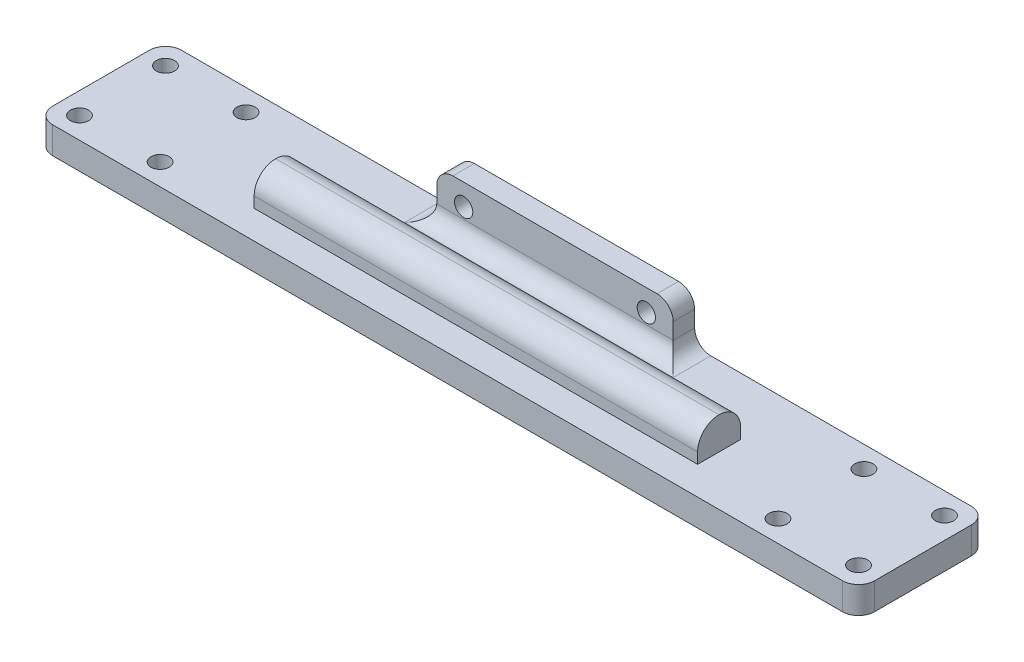
SolidWorks part; units mm, degrees
ref_plane "Front Plane" through (0, 0, 0) normal (0, 0, 1) x (1, 0, 0)
ref_plane "Top Plane" through (0, 0, 0) normal (0, 1, 0) x (1, 0, 0)
ref_plane "Right Plane" through (0, 0, 0) normal (1, 0, 0) x (0, 0, -1)
sketch "Sketch1" plane through (0, 0, 0) normal (0, 1, 0) x (1, 0, 0)
  line L5 (-76.5, -12) -> (-53.5, -12)
  line L13 (-76.5, 12) -> (-53.5, 12)
  line L14 (-76.5, -12) -> (-76.5, 12)
  line L15 (53.5, -12) -> (76.5, -12)
  line L22 (76.5, -12) -> (76.5, 12)
  line L23 (53.5, 12) -> (76.5, 12)
  line L26 (-53.5, 12) -> (53.5, 12)
  line L28 (-53.5, -12) -> (53.5, -12)
  circle A5 centre (-72.5, 8) radius 1.7
  circle A6 centre (-57.5, 8) radius 1.7
  circle A7 centre (-57.5, -8) radius 1.7
  circle A8 centre (-72.5, -8) radius 1.7
  circle A10 centre (57.5, 8) radius 1.7
  circle A11 centre (72.5, 8) radius 1.7
  circle A12 centre (72.5, -8) radius 1.7
  circle A13 centre (57.5, -8) radius 1.7
extrude "Boss-Extrude1" add sketch "Sketch1" along normal blind 5
fillet "Fillet1" radius 3 4 edges at (76.5, 2.5, 12) (76.5, 2.5, -12) (-76.5, 2.5, -12) (-76.5, 2.5, 12)
sketch "Sketch2" plane through (0, 5, 0) normal (0, 1, 0) x (1, 0, 0)
  line L4 (-41.2673, 1.2772) -> (41.2673, 1.2772)
  line L5 (-41.2673, 1.2772) -> (-41.2673, -6.7228)
  line L6 (-41.2673, -6.7228) -> (41.2673, -6.7228)
  line L7 (41.2673, 1.2772) -> (41.2673, -6.7228)
  line L8 (-41.2673, 1.2772) -> (41.2673, -6.7228) construction
  line L9 (-41.2673, -6.7228) -> (41.2673, 1.2772) construction
  point P6 (0, -2.7228)
extrude "Boss-Extrude2" add sketch "Sketch2" along normal blind 6 contours L7 L4 L5 | L7 L5 L6 region at (0, 5, 2.7228)
fillet "Fillet2" radius 4 2 edges at (0, 11, 6.7228) (0, 11, -1.2772)
sketch "Sketch3" plane through (0, 0, -12) normal (0, 0, -1) x (-1, 0, 0)
  line L0 (0, 0) -> (0, 14)
  line L1 (-73.5, 0) -> (73.5, 0) construction
  line L3 (-22, 14) -> (22, 14)
  line L4 (-22, 14) -> (-22, 0)
  line L5 (-22, 0) -> (22, 0)
  line L6 (22, 14) -> (22, 0)
  line L7 (-22, 14) -> (22, 0) construction
  line L8 (-22, 0) -> (22, 14) construction
  point P4 (0, 7)
  line M1 (73.5, 5) -> (-73.5, 5)
extrude "Boss-Extrude3" add sketch "Sketch3" against normal blind 4 contours L3 L4 L0 M1 | L6 L3 L0 M1 region at (11, 9.5, -12) region at (-11, 9.5, -12)
fillet "Fillet3" radius 3 2 edges at (22, 5, -10) (-22, 5, -10)
sketch "Sketch4" plane through (0, 0, -12) normal (0, 0, -1) x (-1, 0, 0)
  line L0 (0, 14) -> (0, 8)
  line L1 (-22, 14) -> (-17, 14)
  line L2 (-22, 14) -> (-22, 10)
  line L3 (-22, 10) -> (-17, 10)
  line L4 (-17, 14) -> (-17, 10)
  line L5 (-22, 14) -> (22, 14) construction
  circle A0 centre (-17, 10) radius 1.7
  circle A1 centre (17, 10) radius 1.7
extrude "Cut-Extrude2" cut sketch "Sketch4" against normal blind 4 contours L4 A0 L3 | L3 A0 L4 | A1 region at (16.7595, 9.7595, -12) region at (17.7215, 10.7215, -12) region at (-17, 10, -12)
fillet "Fillet4" radius 3 2 edges at (-22, 14, -10) (22, 14, -10)
fillet "Fillet5" radius 3 1 edges at (0, 5, -8)
